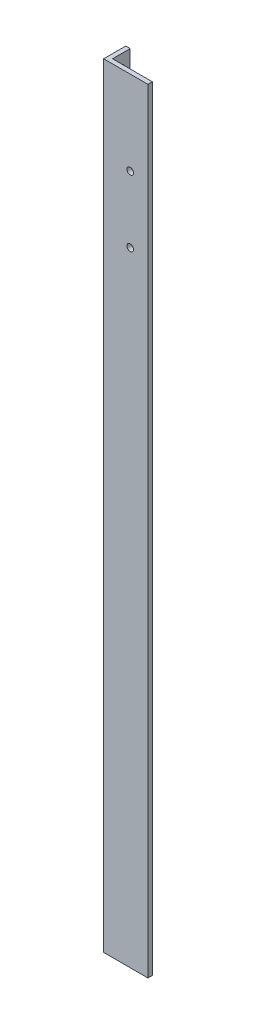
SolidWorks part; units mm, degrees
ref_plane "Front Plane" through (0, 0, 0) normal (0, 0, 1) x (1, 0, 0)
ref_plane "Top Plane" through (0, 0, 0) normal (0, 1, 0) x (1, 0, 0)
ref_plane "Right Plane" through (0, 0, 0) normal (1, 0, 0) x (0, 0, -1)
sketch "Sketch1" plane through (0, 0, 0) normal (0, 1, 0) x (1, 0, 0)
  line L0 (0, 0) -> (0, 10)
  line L1 (0, 10) -> (2, 10)
  line L2 (2, 10) -> (2, 2)
  line L3 (2, 2) -> (20, 2)
  line L4 (20, 2) -> (20, 0)
  line L5 (20, 0) -> (0, 0)
extrude "Boss-Extrude1" add sketch "Sketch1" along normal up to surface (350 mm away)
hole_wizard "Ø3.0 (3) Diameter Hole2" positions "Sketch4" profile "Sketch5" hole size "Ø3.0" standard "ISO"
sketch "Sketch4" plane through (0, -11.4076, -241.32) normal (-1, 0, 0) x (0, 0, 1)
  point P0 (235.32, 341.4076)
  point P2 (235.32, 355.4076)
sketch "Sketch5" plane through (0, 330, -6) normal (0, 1, 0) x (0, 0, 1)
  line L0 (0, 0) -> (0, 1.999)
  line L1 (0, 1.999) -> (1.5, 1.999)
  line L2 (1.5, 1.999) -> (1.5, 0)
  line L3 (1.5, 0) -> (0, 0)
  line L4 (0, -6.35) -> (0, 107.95) construction
  dimension "Thru Hole Dia." = 3
  dimension "Thru Hole Depth" = 1.999
hole_wizard "Ø3.0 (3) Diameter Hole3" positions "Sketch6" profile "Sketch7" hole size "Ø3.0" standard "ISO"
sketch "Sketch6" plane through (0, -11.4076, -241.32) normal (-1, 0, 0) x (0, 0, 1)
  point P0 (235.6632, 17.4076)
  point P1 (235.32, 31.4034)
sketch "Sketch7" plane through (0, 6, -5.6569) normal (0, 1, 0) x (0, 0, 1)
  line L0 (0, 0) -> (0, 1.999)
  line L1 (0, 1.999) -> (1.5, 1.999)
  line L2 (1.5, 1.999) -> (1.5, 0)
  line L3 (1.5, 0) -> (0, 0)
  line L4 (0, -6.35) -> (0, 107.95) construction
  dimension "Thru Hole Dia." = 3
  dimension "Thru Hole Depth" = 1.999
hole_wizard "Ø3.0 (3) Diameter Hole4" positions "Sketch8" profile "Sketch9" hole size "Ø3.0" standard "ISO"
sketch "Sketch8" plane through (221.138, -11.4076, -2) normal (0, 0, -1) x (-1, 0, 0)
  point P0 (209.138, 293.4076)
  point P1 (209.138, 323.4076)
sketch "Sketch9" plane through (12, 282, -2) normal (1, 0, 0) x (0, 1, 0)
  line L0 (0, 0) -> (0, 1.999)
  line L1 (0, 1.999) -> (1.5, 1.999)
  line L2 (1.5, 1.999) -> (1.5, 0)
  line L3 (1.5, 0) -> (0, 0)
  line L4 (0, -6.35) -> (0, 107.95) construction
  dimension "Thru Hole Dia." = 3
  dimension "Thru Hole Depth" = 1.999
